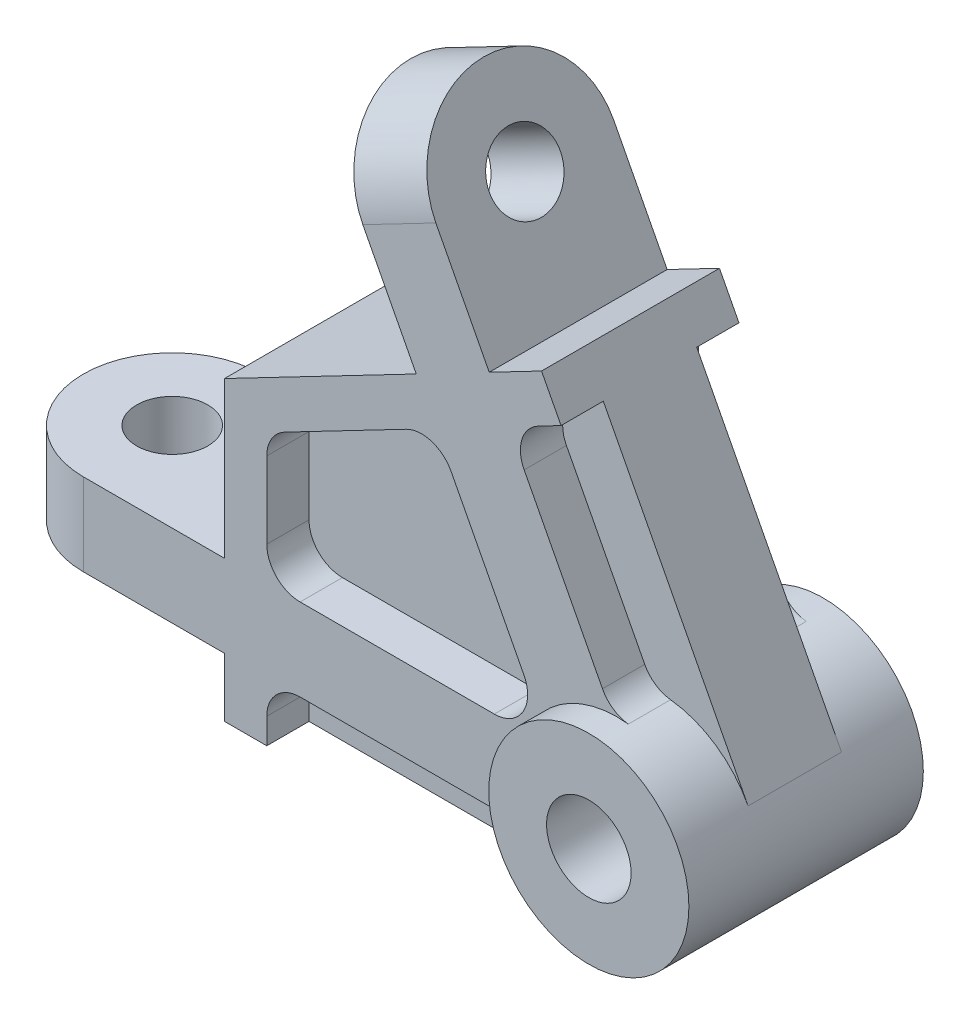
SolidWorks part; units mm, degrees
note: The reader was unsure of these and kept them because the rebuilt part matched: shared geometry of "Esquisse2<5>".
material "AISI 1020"
ref_plane "Plan de face" through (0, 0, 0) normal (0, 0, 1) x (1, 0, 0)
ref_plane "Plan de dessus" through (0, 0, 0) normal (0, 1, 0) x (1, 0, 0)
ref_plane "Plan de droite" through (0, 0, 0) normal (1, 0, 0) x (0, 0, -1)
sketch "Esquisse2" plane through (0, 0, 0) normal (0, 0, 1) x (1, 0, 0)
  line L0 (0, 0) -> (-98.7574, 189.7112) construction
  line L1 (0, 0) -> (-230.8612, 0) construction
  line L2 (0, -22.5) -> (-88.25, -22.5)
  line L3 (-88.25, -22.5) -> (-88.25, -9.25)
  line L4 (-88.25, -9.25) -> (-120, -9.25)
  line L5 (-120, -9.25) -> (-120, 9.25)
  line L6 (-120, 9.25) -> (-88.25, 9.25)
  line L7 (-88.25, 9.25) -> (-88.25, 44.25)
  line L8 (-88.25, 44.25) -> (-45.1445, 66.6893)
  line L9 (-45.1445, 66.6893) -> (-57.1502, 89.752)
  line L10 (-57.1502, 89.752) -> (-40.7405, 98.2943)
  line L11 (-40.7405, 98.2943) -> (-28.7348, 75.2316)
  line L12 (-28.7348, 75.2316) -> (-16.9819, 81.3498)
  line L13 (-16.9819, 81.3498) -> (19.9577, 10.3893)
  circle A0 centre (0, 0) radius 22.5
  circle A1 centre (0, 0) radius 9.5
  dimension "D2" = 45
  dimension "D3" = 19
  dimension "D4" = 35
  dimension "D5" = 18.5
  dimension "D6" = 106
  dimension "D7" = 120
  dimension "D8" = 31.75
  dimension "D1" = 62.5
extrude "Boss.-Extru.1" add sketch "Esquisse2" along normal mid plane 40 contours A0 L13 L12 L11 L10 L9 L8 L7 L6 L5 L4 L3 L2
extrude "Boss.-Extru.2" add sketch "Esquisse2<5>" along normal offset from surface 6.35 and the other way offset from surface (26.35 mm away) 6.35 contours A0 A1 up to face at (-60.8468, 33.7449, 20) offset beyond the face yes other way up to face at (-60.8468, 33.7449, -20)
sketch "Esquisse2<5>" plane through (0, 0, 0) normal (0, 0, 1) x (1, 0, 0) same geometry as "Esquisse2"
sketch "Esquisse3" plane through (0, -9.25, 0) normal (0, -1, 0) x (1, 0, 0)
  line L0 (-120, 20) -> (-120, -20) construction
  line L1 (-120, 20) -> (-120, -20)
  arc A0 (-120, 20) -> (-120, -20) centre (-120, 0) ccw
extrude "Boss.-Extru.3" add sketch "Esquisse3" against normal up to surface (18.5 mm away) up to face at (-104.125, 9.25, 0)
sketch "Esquisse4" plane through (8.2049, 4.2712, 0) normal (0.887, 0.4617, 0) x (0, 0, -1)
  line L0 (-20, 106) -> (20, 106) construction
  line L1 (-20, 106) -> (20, 106)
  arc A0 (-20, 106) -> (20, 106) centre (0, 106) cw
extrude "Boss.-Extru.4" add sketch "Esquisse4" against normal up to surface (18.5 mm away) up to face at (-51.1474, 78.2206, 0)
sketch "Esquisse5" plane through (8.2049, 4.2712, 0) normal (0.887, 0.4617, 0) x (0, 0, -1)
  circle A0 centre (0, 106) radius 8
  dimension "D1" = 16
extrude "Enlèv. mat.-Extru.1" cut sketch "Esquisse5" against normal through all
sketch "Esquisse6" plane through (0, -9.25, 0) normal (0, -1, 0) x (1, 0, 0)
  circle A0 centre (-120, 0) radius 8
  dimension "D1" = 16
extrude "Enlèv. mat.-Extru.2" cut sketch "Esquisse6" against normal through all
sketch "Esquisse7" plane through (0, 0, 20) normal (0, 0, 1) x (1, 0, 0)
  line L0 (0, 0) -> (-120, 0) construction
  line L1 (0, 0) -> (-48.9454, 94.0231) construction
  line L2 (-57.1502, 89.752) -> (-40.7405, 98.2943) construction
  line L3 (-120, -9.25) -> (-120, 9.25) construction
  line L9 (-24.3482, 66.805) -> (-12.5953, 72.9232)
  line L10 (-17.6956, 70.2681) -> (-12.5953, 72.9232)
  line L12 (-83.8634, 35.8234) -> (-40.7579, 58.2627)
  line L13 (-74.7131, 40.5867) -> (-47.4105, 54.7996)
  line L15 (-78.75, 9.25) -> (-78.75, 44.25)
  line L16 (-78.75, 16.75) -> (-78.75, 33.9341)
  line L17 (-71.25, -9.25) -> (-24.8885, -9.25)
  line L18 (-78.75, -22.5) -> (-78.75, -9.25)
  line L19 (-78.75, -22.5) -> (-78.75, -16.75)
  line L20 (-71.25, 9.25) -> (-27.6031, 9.25)
  line L21 (-20.8851, 60.1525) -> (-3.2874, 26.3475)
  line L22 (-37.2948, 51.6101) -> (-20.9506, 20.2131)
  line L23 (-78.75, -22.5) -> (0, -22.5)
  line L24 (-12.5953, 72.9232) -> (19.9577, 10.3893)
  arc A0 (19.9577, 10.3893) -> (0, -22.5) centre (0, 0) ccw construction
  arc A1 (19.9577, 10.3893) -> (2.5239, 22.358) centre (0, 0) ccw
  arc A2 (-18.6664, -12.5625) -> (0, -22.5) centre (0, 0) ccw
  arc A4 (-3.2874, 26.3475) -> (2.5239, 22.358) centre (3.3652, 29.8107) ccw
  arc A5 (-17.6956, 70.2681) -> (-20.8851, 60.1525) centre (-14.2325, 63.6156) ccw
  arc A6 (-78.75, -16.75) -> (-71.25, -9.25) centre (-71.25, -16.75) cw
  arc A7 (-24.8885, -9.25) -> (-18.6664, -12.5625) centre (-24.8885, -16.75) cw
  arc A8 (-47.4105, 54.7996) -> (-37.2948, 51.6101) centre (-43.9474, 48.147) cw
  arc A9 (-74.7131, 40.5867) -> (-78.75, 33.9341) centre (-71.25, 33.9341) ccw
  arc A10 (-78.75, 16.75) -> (-71.25, 9.25) centre (-71.25, 16.75) ccw
  arc A11 (-27.6031, 9.25) -> (-20.9506, 20.2131) centre (-27.6031, 16.75) ccw
  point P34 (-20.5107, -9.25)
  dimension "D5" = 7.5
  dimension "D6" = 7.5
  dimension "D7" = 7.5
  dimension "D1" = 9.5
  dimension "D2" = 9.5
  dimension "D3" = 9.5
  dimension "D4" = 9.5
extrude "Enlèv. mat.-Extru.3" cut sketch "Esquisse7" against normal blind 9.5
mirror "Symétrie1" about plane through (0, 0, 0) normal (0, 0, 1) of "Enlèv. mat.-Extru.3"
equation "\"A\" = 106"
equation "\"B\" = 18.5"
equation "\"C\" = 62.5"
equation "\"D5@Esquisse2\"=\"B\""
equation "\"D6@Esquisse2\"=\"A\""
equation "\"D1@Boss.-Extru.1\"=\"A\""
equation "\"D1@Esquisse2\"=\"C\""
